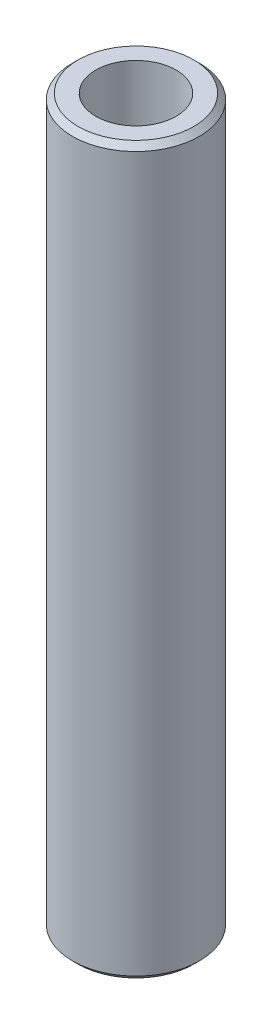
SolidWorks part; units mm, degrees
ref_plane "Front Plane" through (0, 0, 0) normal (0, 0, 1) x (1, 0, 0)
ref_plane "Top Plane" through (0, 0, 0) normal (0, 1, 0) x (1, 0, 0)
ref_plane "Right Plane" through (0, 0, 0) normal (1, 0, 0) x (0, 0, -1)
sketch "Sketch1" plane through (0, 0, 0) normal (0, 1, 0) x (1, 0, 0)
  circle A0 centre (0, 0) radius 52.5
  dimension "SHAFT_OD" = 105
extrude "Boss-Extrude1" add sketch "Sketch1" along normal blind 600
sketch "Sketch2" plane through (0, 0, 0) normal (0, 1, 0) x (1, 0, 0)
  circle A0 centre (0, 0) radius 33.2126
  dimension "BORE_D" = 66.4253
extrude "Cut-Extrude1" cut sketch "Sketch2" along normal through all
chamfer "Chamfer1" distance 4.699 angle 45 2 edges at (0, 600, 52.5) (0, 0, 52.5)
